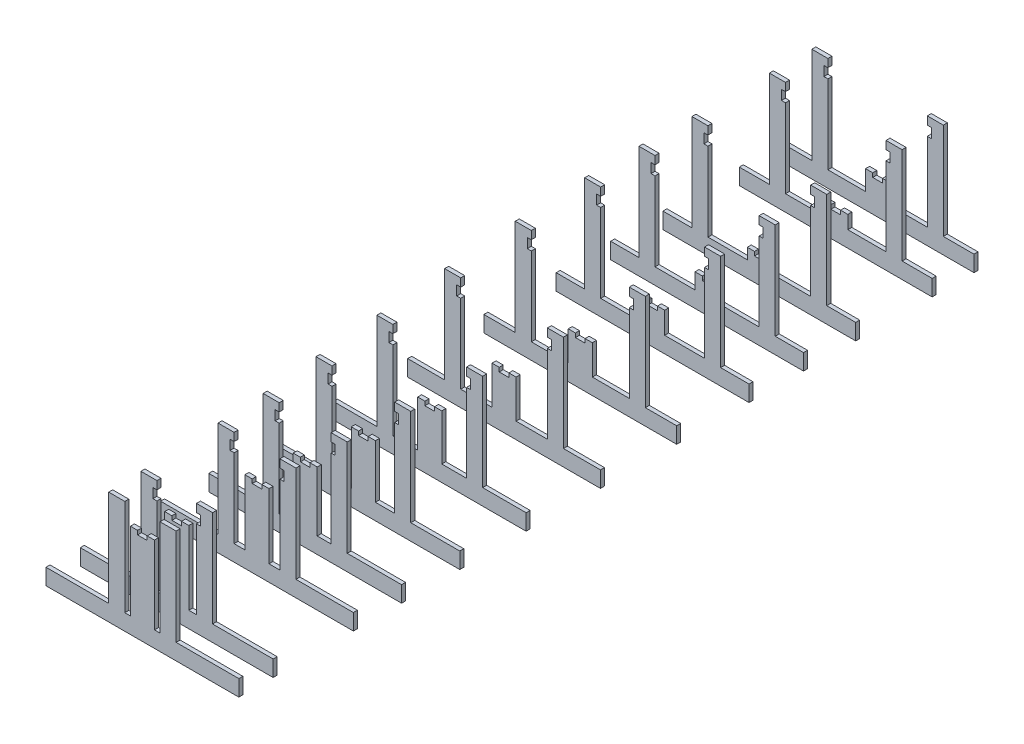
SolidWorks part; units mm, degrees
ref_plane "Front Plane" through (0, 0, 0) normal (0, 0, 1) x (1, 0, 0)
ref_plane "Top Plane" through (0, 0, 0) normal (0, 1, 0) x (1, 0, 0)
ref_plane "Right Plane" through (0, 0, 0) normal (1, 0, 0) x (0, 0, -1)
sketch "Sketch1" plane through (0, 0, 0) normal (0, 0, 1) x (1, 0, 0)
  line L0 (152.4, 0) -> (-152.4, 0)
  line L1 (-152.4, 0) -> (-152.4, 25.4)
  line L2 (-152.4, 25.4) -> (-103.9322, 25.4)
  line L3 (-103.9322, 25.4) -> (-103.9322, 177.8)
  line L4 (-103.9322, 177.8) -> (-78.5322, 177.8)
  line L5 (-78.5322, 177.8) -> (-78.5322, 165.1)
  line L6 (-78.5322, 25.4) -> (-19.05, 25.4)
  line L7 (-19.05, 25.4) -> (-19.05, 56.7311)
  line L9 (19.05, 56.7311) -> (19.05, 25.4)
  line L10 (19.05, 25.4) -> (78.5322, 25.4)
  line L12 (103.9322, 177.8) -> (78.5322, 177.8)
  line L15 (152.4, 25.4) -> (152.4, 0)
  line L16 (78.5322, 25.4) -> (78.5322, 149.86)
  line L17 (103.9322, 177.8) -> (103.9322, 25.4)
  line L18 (103.9322, 25.4) -> (152.4, 25.4)
  line L20 (7.62, 56.7311) -> (7.62, 50.3811)
  line L21 (7.62, 50.3811) -> (-7.62, 50.3811)
  line L22 (-7.62, 50.3811) -> (-7.62, 56.7311)
  line L23 (19.05, 56.7311) -> (7.62, 56.7311)
  line L24 (-7.62, 56.7311) -> (-19.05, 56.7311)
  line L25 (78.5322, 165.1) -> (78.5322, 177.8)
  line L26 (78.5322, 165.1) -> (84.8822, 165.1)
  line L28 (78.5322, 149.86) -> (84.8822, 149.86)
  line L29 (84.8822, 165.1) -> (84.8822, 149.86)
  line L30 (-78.5322, 149.86) -> (-78.5322, 25.4)
  line L31 (-78.5322, 165.1) -> (-84.8822, 165.1)
  line L33 (-78.5322, 149.86) -> (-84.8822, 149.86)
  line L34 (-84.8822, 165.1) -> (-84.8822, 149.86)
  point P0 (-91.2322, 177.8)
  point P3 (0, 0)
  point P4 (0, 0)
  point P20 (91.2322, 177.8)
  point P25 (0.3991, 53.8457)
  dimension "D2" = 182.4645
  dimension "D3" = 6.35
  dimension "D4" = 38.1
  dimension "D5" = 25.4
  dimension "D6" = 25.4
  dimension "D7" = 152.4
  dimension "D8" = 6.35
  dimension "D9" = 304.8
  dimension "D10" = 15.24
  dimension "D11" = 121.0689
  dimension "D12" = 15.24
  dimension "D13" = 12.7
  dimension "D14" = 6.35
  dimension "D15" = 15.24
  dimension "D16" = 12.7
  dimension "D17" = 7.62
sketch3d "3DSketch1"
  line L0 (152.5328, 0, 66.269) -> (-152.2672, 0, 66.269)
  line L1 (152.5328, 0, 66.269) -> (152.5328, 25.4, 66.269)
  line L2 (152.5328, 25.4, 66.269) -> (104.9842, 25.4, 66.269)
  line L3 (104.9842, 25.4, 66.269) -> (104.9842, 177.8, 66.269)
  line L4 (104.9842, 177.8, 66.269) -> (79.5842, 177.8, 66.269)
  line L6 (79.5842, 25.4, 66.269) -> (19.1828, 25.4, 66.269)
  line L7 (19.1828, 25.4, 66.269) -> (19.1828, 46.3854, 66.269)
  line L9 (-18.9172, 46.3854, 66.269) -> (-18.9172, 25.4, 66.269)
  line L10 (-18.9172, 25.4, 66.269) -> (-79.3186, 25.4, 66.269)
  line L12 (-79.3186, 177.8, 66.269) -> (-104.7186, 177.8, 66.269)
  line L13 (-104.7186, 177.8, 66.269) -> (-104.7186, 25.4, 66.269)
  line L14 (-104.7186, 25.4, 66.269) -> (-152.2672, 25.4, 66.269)
  line L15 (-152.2672, 25.4, 66.269) -> (-152.2672, 0, 66.269)
  line L17 (19.1828, 46.3854, 66.269) -> (7.7528, 46.3854, 66.269)
  line L19 (7.7528, 46.3854, 66.269) -> (7.7528, 40.0354, 66.269)
  line L20 (7.7528, 40.0354, 66.269) -> (-7.4872, 40.0354, 66.269)
  line L21 (-7.4872, 46.3854, 66.269) -> (-7.4872, 40.0354, 66.269)
  line L22 (-7.4872, 46.3854, 66.269) -> (-18.9172, 46.3854, 66.269)
  line L23 (79.5842, 177.8, 66.269) -> (79.5842, 165.1, 66.269)
  line L24 (79.5842, 165.1, 66.269) -> (85.9342, 165.1, 66.269)
  line L26 (79.5842, 149.86, 66.269) -> (85.9342, 149.86, 66.269)
  line L27 (85.9342, 165.1, 66.269) -> (85.9342, 149.86, 66.269)
  line L28 (-79.3186, 165.1, 66.269) -> (-85.6686, 165.1, 66.269)
  line L30 (-79.3186, 149.86, 66.269) -> (-85.6686, 149.86, 66.269)
  line L31 (-85.6686, 165.1, 66.269) -> (-85.6686, 149.86, 66.269)
  line L32 (79.5842, 149.86, 66.269) -> (79.5842, 25.4, 66.269)
  line L33 (-79.3186, 177.8, 66.269) -> (-79.3186, 165.1, 66.269)
  line L34 (-79.3186, 149.86, 66.269) -> (-79.3186, 25.4, 66.269)
  point P3 (0.1328, 0, 66.269)
  point P20 (-92.0186, 177.8, 66.269)
  point P21 (92.2842, 177.8, 66.269)
  dimension "D2" = 25.4
  dimension "D1" = 304.8
  dimension "D3" = 184.3028
  dimension "D4" = 25.4
  dimension "D5" = 38.1
  dimension "D6" = 152.4
  dimension "D7" = 131.4146
  dimension "D9" = 6.35
  dimension "D8" = 66.269
  dimension "D10" = 15.24
  dimension "D11" = 12.7
  dimension "D12" = 6.35
  dimension "D13" = 15.24
  dimension "D14" = 6.35
  dimension "D15" = 15.24
  dimension "D16" = 12.7
  dimension "D17" = 19.05
  dimension "D18" = 19.05
  dimension "D19" = 7.62
extrude "F0" add sketch "Sketch1" along normal blind 6.35
extrude "F1" add sketch "3DSketch1" along direction (0, 0, -1) on the side of the normal blind 6.35 separate body contours L0 L15 L14 L13 L12 L33 L28 L31 L30 L34 L10 L9 L22 L21 L20 L19 L17 L7 L6 L32 L26 L27 L24 L23 L4 L3 L2 L1
sketch3d "3DSketch2"
  line L0 (-152.4, 0, 186.919) -> (152.4, 0, 186.919)
  line L1 (152.4, 0, 186.919) -> (152.4, 25.4, 186.919)
  line L2 (152.4, 25.4, 186.919) -> (106.5766, 25.4, 186.919)
  line L3 (106.5766, 25.4, 186.919) -> (106.5766, 177.8, 186.919)
  line L4 (106.5766, 177.8, 186.919) -> (81.1766, 177.8, 186.919)
  line L6 (81.1766, 25.4, 186.919) -> (19.05, 25.4, 186.919)
  line L7 (19.05, 25.4, 186.919) -> (19.05, 42.5995, 186.919)
  line L9 (-19.05, 42.5995, 186.919) -> (-19.05, 25.4, 186.919)
  line L10 (-19.05, 25.4, 186.919) -> (-81.1766, 25.4, 186.919)
  line L12 (-81.1766, 177.8, 186.919) -> (-106.5766, 177.8, 186.919)
  line L13 (-106.5766, 177.8, 186.919) -> (-106.5766, 25.4, 186.919)
  line L14 (-106.5766, 25.4, 186.919) -> (-152.4, 25.4, 186.919)
  line L15 (-152.4, 25.4, 186.919) -> (-152.4, 0, 186.919)
  line L16 (-19.05, 42.5995, 186.919) -> (-7.62, 42.5995, 186.919)
  line L17 (-152.2672, 0, 72.619) -> (152.5328, 0, 72.619) construction
  line L19 (-7.62, 42.5995, 186.919) -> (-7.62, 36.2495, 186.919)
  line L20 (-7.62, 36.2495, 186.919) -> (7.62, 36.2495, 186.919)
  line L21 (7.62, 42.5995, 186.919) -> (7.62, 36.2495, 186.919)
  line L22 (7.62, 42.5995, 186.919) -> (19.05, 42.5995, 186.919)
  line L23 (-81.1766, 177.8, 186.919) -> (-81.1766, 165.1, 186.919)
  line L24 (-81.1766, 165.1, 186.919) -> (-87.5266, 165.1, 186.919)
  line L26 (-81.1766, 149.86, 186.919) -> (-87.5266, 149.86, 186.919)
  line L27 (-87.5266, 165.1, 186.919) -> (-87.5266, 149.86, 186.919)
  line L28 (81.1766, 165.1, 186.919) -> (87.5266, 165.1, 186.919)
  line L30 (81.1766, 149.86, 186.919) -> (87.5266, 149.86, 186.919)
  line L31 (87.5266, 165.1, 186.919) -> (87.5266, 149.86, 186.919)
  line L32 (-81.1766, 149.86, 186.919) -> (-81.1766, 25.4, 186.919)
  line L33 (81.1766, 177.8, 186.919) -> (81.1766, 165.1, 186.919)
  line L34 (81.1766, 149.86, 186.919) -> (81.1766, 25.4, 186.919)
  point P3 (0, 0, 186.919)
  point P18 (-93.8766, 177.8, 186.919)
  point P22 (93.8766, 177.8, 186.919)
  dimension "D2" = 152.4
  dimension "D1" = 25.4
  dimension "D3" = 25.4
  dimension "D4" = 38.1
  dimension "D5" = 187.7532
  dimension "D6" = 135.2005
  dimension "D9" = 15.24
  dimension "D7" = 114.3
  dimension "D8" = 304.8
  dimension "D10" = 6.35
  dimension "D11" = 12.7
  dimension "D12" = 15.24
  dimension "D13" = 6.35
  dimension "D14" = 12.7
  dimension "D15" = 7.62
  dimension "D16" = 6.35
extrude "F2" add sketch "3DSketch2" along direction (0, 0, -1) on the side against the normal blind 6.35 separate body contours L13 L14 L15 L0 L1 L2 L3 L4 L33 L28 L31 L30 L34 L6 L7 L22 L21 L20 L19 L16 L9 L10 L32 L26 L27 L24 L23 L12
sketch3d "3DSketch3"
  line L1 (-19.05, 50.2445, 269.469) -> (-7.62, 50.2445, 269.469)
  line L2 (-152.4, 0, 269.469) -> (152.4, 0, 269.469)
  line L3 (152.4, 0, 269.469) -> (152.4, 25.4, 269.469)
  line L4 (152.4, 25.4, 269.469) -> (107.6828, 25.4, 269.469)
  line L5 (107.6828, 25.4, 269.469) -> (107.6828, 177.8, 269.469)
  line L6 (107.6828, 177.8, 269.469) -> (82.2828, 177.8, 269.469)
  line L8 (82.2828, 25.4, 269.469) -> (19.05, 25.4, 269.469)
  line L9 (19.05, 25.4, 269.469) -> (19.05, 50.2445, 269.469)
  line L11 (-19.05, 50.2445, 269.469) -> (-19.05, 25.4, 269.469)
  line L12 (-19.05, 25.4, 269.469) -> (-82.2828, 25.4, 269.469)
  line L14 (-82.2828, 177.8, 269.469) -> (-107.6828, 177.8, 269.469)
  line L15 (-107.6828, 177.8, 269.469) -> (-107.6828, 25.4, 269.469)
  line L16 (-107.6828, 25.4, 269.469) -> (-152.4, 25.4, 269.469)
  line L17 (-152.4, 25.4, 269.469) -> (-152.4, 0, 269.469)
  line L19 (-7.62, 50.2445, 269.469) -> (-7.62, 43.8945, 269.469)
  line L20 (-7.62, 43.8945, 269.469) -> (7.62, 43.8945, 269.469)
  line L21 (7.62, 50.2445, 269.469) -> (7.62, 43.8945, 269.469)
  line L22 (7.62, 50.2445, 269.469) -> (19.05, 50.2445, 269.469)
  line L23 (-82.2828, 177.8, 269.469) -> (-82.2828, 165.1, 269.469)
  line L24 (-82.2828, 165.1, 269.469) -> (-88.6328, 165.1, 269.469)
  line L26 (-82.2828, 149.86, 269.469) -> (-88.6328, 149.86, 269.469)
  line L27 (-88.6328, 165.1, 269.469) -> (-88.6328, 149.86, 269.469)
  line L28 (82.2828, 165.1, 269.469) -> (88.6328, 165.1, 269.469)
  line L30 (82.2828, 149.86, 269.469) -> (88.6328, 149.86, 269.469)
  line L31 (88.6328, 165.1, 269.469) -> (88.6328, 149.86, 269.469)
  line L32 (-82.2828, 149.86, 269.469) -> (-82.2828, 25.4, 269.469)
  line L33 (82.2828, 177.8, 269.469) -> (82.2828, 165.1, 269.469)
  line L34 (82.2828, 149.86, 269.469) -> (82.2828, 25.4, 269.469)
  line L36 (-152.4, 0, 193.269) -> (152.4, 0, 193.269) construction
  point P2 (-94.9828, 177.8, 269.469)
  point P3 (94.9828, 177.8, 269.469)
  point P6 (0, 0, 269.469)
  dimension "D16" = 76.2
  dimension "D2" = 304.8
  dimension "D3" = 25.4
  dimension "D4" = 152.4
  dimension "D5" = 25.4
  dimension "D6" = 189.9655
  dimension "D7" = 38.1
  dimension "D8" = 127.5555
  dimension "D9" = 6.35
  dimension "D10" = 15.24
  dimension "D11" = 12.7
  dimension "D12" = 6.35
  dimension "D13" = 15.24
  dimension "D14" = 19.05
  dimension "D15" = 19.05
  dimension "D17" = 7.62
extrude "F3" add sketch "3DSketch3" along normal blind 6.35 separate body contours L12 L32 L26 L27 L24 L23 L14 L15 L16 L17 L2 L3 L4 L5 L6 L33 L28 L31 L30 L34 L8 L9 L22 L21 L20 L19 L1 L11
sketch3d "3DSketch4"
  line L1 (-19.05, 59.7774, 355.6) -> (-7.62, 59.7774, 355.6)
  line L2 (152.4, 0, 355.6) -> (-152.4, 0, 355.6)
  line L3 (-152.4, 0, 355.6) -> (-152.4, 25.4, 355.6)
  line L4 (-152.4, 25.4, 355.6) -> (-107.4723, 25.4, 355.6)
  line L5 (-107.4723, 25.4, 355.6) -> (-107.4723, 177.8, 355.6)
  line L6 (-107.4723, 177.8, 355.6) -> (-82.0723, 177.8, 355.6)
  line L8 (-82.0723, 25.4, 355.6) -> (-19.05, 25.4, 355.6)
  line L9 (-19.05, 25.4, 355.6) -> (-19.05, 59.7774, 355.6)
  line L11 (19.05, 59.7774, 355.6) -> (19.05, 25.4, 355.6)
  line L12 (19.05, 25.4, 355.6) -> (82.0723, 25.4, 355.6)
  line L14 (82.0723, 177.8, 355.6) -> (107.4723, 177.8, 355.6)
  line L15 (107.4723, 177.8, 355.6) -> (107.4723, 25.4, 355.6)
  line L16 (107.4723, 25.4, 355.6) -> (152.4, 25.4, 355.6)
  line L17 (152.4, 25.4, 355.6) -> (152.4, 0, 355.6)
  line L19 (-7.62, 59.7774, 355.6) -> (-7.62, 53.4274, 355.6)
  line L20 (-7.62, 53.4274, 355.6) -> (7.62, 53.4274, 355.6)
  line L21 (7.62, 59.7774, 355.6) -> (7.62, 53.4274, 355.6)
  line L22 (7.62, 59.7774, 355.6) -> (19.05, 59.7774, 355.6)
  line L23 (-82.0723, 177.8, 355.6) -> (-82.0723, 165.1, 355.6)
  line L24 (-82.0723, 165.1, 355.6) -> (-88.4223, 165.1, 355.6)
  line L26 (-82.0723, 149.86, 355.6) -> (-88.4223, 149.86, 355.6)
  line L27 (-88.4223, 165.1, 355.6) -> (-88.4223, 149.86, 355.6)
  line L28 (82.0723, 165.1, 355.6) -> (88.4223, 165.1, 355.6)
  line L30 (82.0723, 149.86, 355.6) -> (88.4223, 149.86, 355.6)
  line L31 (88.4223, 165.1, 355.6) -> (88.4223, 149.86, 355.6)
  line L32 (-82.0723, 149.86, 355.6) -> (-82.0723, 25.4, 355.6)
  line L33 (82.0723, 177.8, 355.6) -> (82.0723, 165.1, 355.6)
  line L34 (82.0723, 149.86, 355.6) -> (82.0723, 25.4, 355.6)
  point P6 (0, 0, 355.6)
  point P21 (-94.7723, 177.8, 355.6)
  point P22 (94.7723, 177.8, 355.6)
  dimension "D1" = 304.8
  dimension "D2" = 25.4
  dimension "D3" = 152.4
  dimension "D4" = 25.4
  dimension "D5" = 38.1
  dimension "D6" = 189.5445
  dimension "D7" = 118.0226
  dimension "D9" = 6.35
  dimension "D8" = 79.781
  dimension "D16" = 7.62
  dimension "D10" = 15.24
  dimension "D11" = 12.7
  dimension "D12" = 6.35
  dimension "D13" = 15.24
  dimension "D14" = 19.05
  dimension "D15" = 19.05
extrude "F4" add sketch "3DSketch4" along direction (0, 0, 1) on the side of the normal blind 6.35 separate body contours L4 L5 L6 L23 L24 L27 L26 L32 L8 L9 L1 L19 L20 L21 L22 L11 L12 L34 L30 L31 L28 L33 L14 L15 L16 L17 L2 L3
sketch3d "3DSketch5"
  line L1 (19.05, 72.4289, 469.9) -> (7.62, 72.4289, 469.9)
  line L2 (152.4, 0, 469.9) -> (-152.4, 0, 469.9)
  line L3 (-152.4, 0, 469.9) -> (-152.4, 25.4, 469.9)
  line L4 (-152.4, 25.4, 469.9) -> (-102.8282, 25.4, 469.9)
  line L5 (-102.8282, 25.4, 469.9) -> (-102.8282, 177.8, 469.9)
  line L6 (-102.8282, 177.8, 469.9) -> (-77.4282, 177.8, 469.9)
  line L8 (-77.4282, 25.4, 469.9) -> (-19.05, 25.4, 469.9)
  line L9 (-19.05, 25.4, 469.9) -> (-19.05, 72.4289, 469.9)
  line L11 (19.05, 72.4289, 469.9) -> (19.05, 25.4, 469.9)
  line L12 (19.05, 25.4, 469.9) -> (77.4282, 25.4, 469.9)
  line L14 (77.4282, 177.8, 469.9) -> (102.8282, 177.8, 469.9)
  line L15 (102.8282, 177.8, 469.9) -> (102.8282, 25.4, 469.9)
  line L16 (102.8282, 25.4, 469.9) -> (152.4, 25.4, 469.9)
  line L17 (152.4, 25.4, 469.9) -> (152.4, 0, 469.9)
  line L19 (7.62, 72.4289, 469.9) -> (7.62, 66.0789, 469.9)
  line L20 (7.62, 66.0789, 469.9) -> (-7.62, 66.0789, 469.9)
  line L21 (-7.62, 72.4289, 469.9) -> (-7.62, 66.0789, 469.9)
  line L22 (77.4282, 165.1, 469.9) -> (83.7782, 165.1, 469.9)
  line L24 (77.4282, 149.7642, 469.9) -> (83.7782, 149.7642, 469.9)
  line L25 (83.7782, 165.1, 469.9) -> (83.7782, 149.7642, 469.9)
  line L26 (-77.4282, 165.1, 469.9) -> (-83.7782, 165.1, 469.9)
  line L28 (-77.4282, 149.7642, 469.9) -> (-83.7782, 149.7642, 469.9)
  line L29 (-83.7782, 165.1, 469.9) -> (-83.7782, 149.7642, 469.9)
  line L30 (-7.62, 72.4289, 469.9) -> (-19.05, 72.4289, 469.9)
  line L31 (77.4282, 177.8, 469.9) -> (77.4282, 165.1, 469.9)
  line L32 (77.4282, 149.7642, 469.9) -> (77.4282, 25.4, 469.9)
  line L33 (-77.4282, 177.8, 469.9) -> (-77.4282, 165.1, 469.9)
  line L34 (-77.4282, 149.7642, 469.9) -> (-77.4282, 25.4, 469.9)
  point P6 (0, 0, 469.9)
  point P21 (-90.1282, 177.8, 469.9)
  point P22 (90.1282, 177.8, 469.9)
  dimension "D1" = 304.8
  dimension "D2" = 25.4
  dimension "D3" = 152.4
  dimension "D4" = 180.2564
  dimension "D5" = 25.4
  dimension "D6" = 38.1
  dimension "D7" = 105.3711
  dimension "D9" = 15.24
  dimension "D8" = 107.95
  dimension "D14" = 7.62
  dimension "D10" = 6.35
  dimension "D11" = 12.7
  dimension "D12" = 6.35
  dimension "D13" = 15.3358
extrude "F5" add sketch "3DSketch5" along direction (0, 0, 1) on the side against the normal blind 6.35 separate body contours L2 L3 L4 L5 L6 L33 L26 L29 L28 L34 L8 L9 L30 L21 L20 L19 L1 L11 L12 L32 L24 L25 L22 L31 L14 L15 L16 L17
sketch3d "3DSketch6"
  line L0 (68.6198, 177.8, 590.55) -> (68.6198, 165.1, 590.55)
  line L2 (-152.2755, 0, 590.55) -> (152.5245, 0, 590.55)
  line L3 (152.5245, 0, 590.55) -> (152.5245, 25.4, 590.55)
  line L4 (152.5245, 25.4, 590.55) -> (94.0198, 25.4, 590.55)
  line L5 (94.0198, 25.4, 590.55) -> (94.0198, 177.8, 590.55)
  line L6 (94.0198, 177.8, 590.55) -> (68.6198, 177.8, 590.55)
  line L8 (68.6198, 25.4, 590.55) -> (19.1745, 25.4, 590.55)
  line L9 (19.1745, 25.4, 590.55) -> (19.1745, 85.804, 590.55)
  line L11 (-18.9255, 85.804, 590.55) -> (-18.9255, 25.4, 590.55)
  line L12 (-18.9255, 25.4, 590.55) -> (-68.3707, 25.4, 590.55)
  line L14 (-68.3707, 177.8, 590.55) -> (-93.7707, 177.8, 590.55)
  line L15 (-93.7707, 177.8, 590.55) -> (-93.7707, 25.4, 590.55)
  line L16 (-93.7707, 25.4, 590.55) -> (-152.2755, 25.4, 590.55)
  line L17 (-152.2755, 25.4, 590.55) -> (-152.2755, 0, 590.55)
  line L18 (7.7445, 85.804, 590.55) -> (7.7445, 79.454, 590.55)
  line L19 (7.7445, 79.454, 590.55) -> (-7.4955, 79.454, 590.55)
  line L20 (-7.4955, 85.804, 590.55) -> (-7.4955, 79.454, 590.55)
  line L21 (68.6198, 165.1, 590.55) -> (74.9698, 165.1, 590.55)
  line L23 (68.6198, 149.86, 590.55) -> (74.9698, 149.86, 590.55)
  line L24 (74.9698, 165.1, 590.55) -> (74.9698, 149.86, 590.55)
  line L25 (-68.3707, 165.1, 590.55) -> (-74.7207, 165.1, 590.55)
  line L27 (-68.3707, 149.86, 590.55) -> (-74.7207, 149.86, 590.55)
  line L28 (-74.7207, 165.1, 590.55) -> (-74.7207, 149.86, 590.55)
  line L29 (68.6198, 149.86, 590.55) -> (68.6198, 25.4, 590.55)
  line L30 (-68.3707, 177.8, 590.55) -> (-68.3707, 165.1, 590.55)
  line L31 (-68.3707, 149.86, 590.55) -> (-68.3707, 25.4, 590.55)
  line L32 (19.1745, 85.804, 590.55) -> (7.7445, 85.804, 590.55)
  line L33 (-7.4955, 85.804, 590.55) -> (-18.9255, 85.804, 590.55)
  point P6 (0.1245, 0, 590.55)
  point P21 (-81.0707, 177.8, 590.55)
  point P22 (81.3198, 177.8, 590.55)
  point P31 (0.1245, 79.454, 590.55)
  dimension "D1" = 25.4
  dimension "D2" = 152.4
  dimension "D3" = 25.4
  dimension "D4" = 38.1
  dimension "D5" = 304.8
  dimension "D6" = 162.3905
  dimension "D7" = 91.996
  dimension "D9" = 12.7
  dimension "D8" = 114.3
  dimension "D10" = 15.24
  dimension "D11" = 6.35
  dimension "D12" = 15.24
  dimension "D13" = 6.35
  dimension "D14" = 7.62
extrude "F6" add sketch "3DSketch6" along direction (0, 0, 1) on the side of the normal blind 6.35 separate body contours L15 L16 L17 L2 L3 L4 L5 L6 L0 L21 L24 L23 L29 L8 L9 L32 L18 L19 L20 L33 L11 L12 L31 L27 L28 L25 L30 L14
sketch3d "3DSketch7"
  line L0 (58.204, 177.8, 707.9085) -> (58.204, 165.1, 707.9085)
  line L2 (152.4, 0, 707.9085) -> (-152.4, 0, 707.9085)
  line L3 (-152.4, 0, 707.9085) -> (-152.4, 25.4, 707.9085)
  line L4 (-152.4, 25.4, 707.9085) -> (-83.604, 25.4, 707.9085)
  line L5 (-83.604, 25.4, 707.9085) -> (-83.604, 177.8, 707.9085)
  line L6 (-83.604, 177.8, 707.9085) -> (-58.204, 177.8, 707.9085)
  line L8 (-58.204, 25.4, 707.9085) -> (-19.05, 25.4, 707.9085)
  line L9 (-19.05, 25.4, 707.9085) -> (-19.05, 98.1126, 707.9085)
  line L11 (19.05, 98.1126, 707.9085) -> (19.05, 25.4, 707.9085)
  line L12 (19.05, 25.4, 707.9085) -> (58.204, 25.4, 707.9085)
  line L14 (58.204, 177.8, 707.9085) -> (83.604, 177.8, 707.9085)
  line L15 (83.604, 177.8, 707.9085) -> (83.604, 25.4, 707.9085)
  line L16 (83.604, 25.4, 707.9085) -> (152.4, 25.4, 707.9085)
  line L17 (152.4, 25.4, 707.9085) -> (152.4, 0, 707.9085)
  line L18 (7.62, 98.1126, 707.9085) -> (7.62, 91.7626, 707.9085)
  line L19 (7.62, 91.7626, 707.9085) -> (-7.62, 91.7626, 707.9085)
  line L20 (-7.62, 98.1126, 707.9085) -> (-7.62, 91.7626, 707.9085)
  line L21 (-58.204, 165.1, 707.9085) -> (-64.554, 165.1, 707.9085)
  line L23 (-58.204, 149.86, 707.9085) -> (-64.554, 149.86, 707.9085)
  line L24 (-64.554, 165.1, 707.9085) -> (-64.554, 149.86, 707.9085)
  line L25 (58.204, 165.1, 707.9085) -> (64.554, 165.1, 707.9085)
  line L27 (58.204, 149.86, 707.9085) -> (64.554, 149.86, 707.9085)
  line L28 (64.554, 165.1, 707.9085) -> (64.554, 149.86, 707.9085)
  line L29 (58.204, 149.86, 707.9085) -> (58.204, 25.4, 707.9085)
  line L30 (-58.204, 177.8, 707.9085) -> (-58.204, 165.1, 707.9085)
  line L31 (-58.204, 149.86, 707.9085) -> (-58.204, 25.4, 707.9085)
  line L32 (-19.05, 98.1126, 707.9085) -> (-7.62, 98.1126, 707.9085)
  line L33 (7.62, 98.1126, 707.9085) -> (19.05, 98.1126, 707.9085)
  point P6 (0, 0, 707.9085)
  point P21 (-70.904, 177.8, 707.9085)
  point P22 (70.904, 177.8, 707.9085)
  dimension "D1" = 304.8
  dimension "D2" = 25.4
  dimension "D3" = 152.4
  dimension "D4" = 25.4
  dimension "D5" = 38.1
  dimension "D6" = 141.8079
  dimension "D7" = 79.6874
  dimension "D8" = 12.7
  dimension "D9" = 15.24
  dimension "D10" = 6.35
  dimension "D11" = 15.24
  dimension "D12" = 6.35
  dimension "D13" = 7.62
extrude "F7" add sketch "3DSketch7" along direction (0, 0, 1) on the side of the normal blind 6.35 separate body contours L4 L5 L6 L30 L21 L24 L23 L31 L8 L9 L32 L20 L19 L18 L33 L11 L12 L29 L27 L28 L25 L0 L14 L15 L16 L17 L2 L3
sketch3d "3DSketch8"
  line L0 (-19.05, 109.752, 812.8) -> (-7.62, 109.752, 812.8)
  line L2 (-152.4, 0, 812.8) -> (152.4, 0, 812.8)
  line L3 (152.4, 0, 812.8) -> (152.4, 25.4, 812.8)
  line L4 (152.4, 25.4, 812.8) -> (74.9005, 25.4, 812.8)
  line L5 (74.9005, 25.4, 812.8) -> (74.9005, 177.8, 812.8)
  line L6 (74.9005, 177.8, 812.8) -> (49.5005, 177.8, 812.8)
  line L8 (49.5005, 25.4, 812.8) -> (19.05, 25.4, 812.8)
  line L9 (19.05, 25.4, 812.8) -> (19.05, 109.752, 812.8)
  line L11 (-19.05, 109.752, 812.8) -> (-19.05, 25.4, 812.8)
  line L12 (-19.05, 25.4, 812.8) -> (-49.5005, 25.4, 812.8)
  line L14 (-49.5005, 177.8, 812.8) -> (-74.9005, 177.8, 812.8)
  line L15 (-74.9005, 177.8, 812.8) -> (-74.9005, 25.4, 812.8)
  line L16 (-74.9005, 25.4, 812.8) -> (-152.4, 25.4, 812.8)
  line L17 (-152.4, 25.4, 812.8) -> (-152.4, 0, 812.8)
  line L18 (-7.62, 109.752, 812.8) -> (-7.62, 103.402, 812.8)
  line L19 (-7.62, 103.402, 812.8) -> (7.62, 103.402, 812.8)
  line L20 (7.62, 109.752, 812.8) -> (7.62, 103.402, 812.8)
  line L21 (-49.5005, 165.1, 812.8) -> (-55.8505, 165.1, 812.8)
  line L23 (-49.5005, 149.86, 812.8) -> (-55.8505, 149.86, 812.8)
  line L24 (-55.8505, 165.1, 812.8) -> (-55.8505, 149.86, 812.8)
  line L25 (49.5005, 165.1, 812.8) -> (55.8505, 165.1, 812.8)
  line L27 (49.5005, 149.86, 812.8) -> (55.8505, 149.86, 812.8)
  line L28 (55.8505, 165.1, 812.8) -> (55.8505, 149.86, 812.8)
  line L29 (7.62, 109.752, 812.8) -> (19.05, 109.752, 812.8)
  line L30 (-49.5005, 177.8, 812.8) -> (-49.5005, 165.1, 812.8)
  line L31 (-49.5005, 149.86, 812.8) -> (-49.5005, 25.4, 812.8)
  line L32 (49.5005, 25.4, 812.8) -> (49.5005, 149.86, 812.8)
  line L33 (49.5005, 165.1, 812.8) -> (49.5005, 177.8, 812.8)
  point P6 (0, 0, 812.8)
  point P21 (-62.2005, 177.8, 812.8)
  point P22 (62.2005, 177.8, 812.8)
  dimension "D1" = 304.8
  dimension "D2" = 25.4
  dimension "D3" = 152.4
  dimension "D4" = 25.4
  dimension "D5" = 38.1
  dimension "D6" = 124.4009
  dimension "D7" = 68.048
  dimension "D8" = 7.62
  dimension "D9" = 12.7
  dimension "D10" = 15.24
  dimension "D11" = 6.35
  dimension "D12" = 15.24
  dimension "D13" = 6.35
  dimension "D14" = 98.5415
extrude "F8" add sketch "3DSketch8" along direction (0, 0, -1) on the side against the normal blind 6.35 separate body contours L15 L16 L17 L2 L3 L4 L5 L6 L33 L25 L28 L27 L32 L8 L9 L29 L20 L19 L18 L0 L11 L12 L31 L23 L24 L21 L30 L14
sketch3d "3DSketch9"
  line L0 (-40.9127, 177.8, 904.875) -> (-40.9127, 165.1, 904.875)
  line L1 (-40.9127, 165.1, 904.875) -> (-47.2627, 165.1, 904.875)
  line L2 (152.5212, 0, 904.875) -> (-152.2788, 0, 904.875)
  line L3 (-152.2788, 0, 904.875) -> (-152.2788, 25.4, 904.875)
  line L4 (-152.2788, 25.4, 904.875) -> (-66.3127, 25.4, 904.875)
  line L5 (-66.3127, 25.4, 904.875) -> (-66.3127, 177.8, 904.875)
  line L6 (-66.3127, 177.8, 904.875) -> (-40.9127, 177.8, 904.875)
  line L8 (-40.9127, 25.4, 904.875) -> (-18.9288, 25.4, 904.875)
  line L9 (-18.9288, 25.4, 904.875) -> (-18.9288, 119.8783, 904.875)
  line L11 (19.1712, 119.8783, 904.875) -> (19.1712, 25.4, 904.875)
  line L12 (19.1712, 25.4, 904.875) -> (41.1552, 25.4, 904.875)
  line L14 (41.1552, 177.8, 904.875) -> (66.5552, 177.8, 904.875)
  line L15 (66.5552, 177.8, 904.875) -> (66.5552, 25.4, 904.875)
  line L16 (66.5552, 25.4, 904.875) -> (152.5212, 25.4, 904.875)
  line L17 (152.5212, 25.4, 904.875) -> (152.5212, 0, 904.875)
  line L19 (-40.9127, 149.86, 904.875) -> (-47.2627, 149.86, 904.875)
  line L20 (-47.2627, 165.1, 904.875) -> (-47.2627, 149.86, 904.875)
  line L21 (41.1552, 165.1, 904.875) -> (47.5052, 165.1, 904.875)
  line L23 (41.1552, 149.86, 904.875) -> (47.5052, 149.86, 904.875)
  line L24 (47.5052, 165.1, 904.875) -> (47.5052, 149.86, 904.875)
  line L26 (-7.4988, 119.8783, 904.875) -> (-7.4988, 113.5283, 904.875)
  line L27 (-7.4988, 113.5283, 904.875) -> (7.7412, 113.5283, 904.875)
  line L28 (7.7412, 119.8783, 904.875) -> (7.7412, 113.5283, 904.875)
  line L29 (-40.9127, 149.86, 904.875) -> (-40.9127, 25.4, 904.875)
  line L30 (41.1552, 177.8, 904.875) -> (41.1552, 165.1, 904.875)
  line L31 (41.1552, 149.86, 904.875) -> (41.1552, 25.4, 904.875)
  line L32 (-18.9288, 119.8783, 904.875) -> (-7.4988, 119.8783, 904.875)
  line L33 (7.7412, 119.8783, 904.875) -> (19.1712, 119.8783, 904.875)
  point P0 (-53.6127, 177.8, 904.875)
  point P1 (53.8552, 177.8, 904.875)
  point P6 (0.1212, 0, 904.875)
  dimension "D1" = 304.8
  dimension "D2" = 25.4
  dimension "D3" = 152.4
  dimension "D4" = 25.4
  dimension "D5" = 38.1
  dimension "D6" = 107.4679
  dimension "D7" = 85.725
  dimension "D9" = 15.24
  dimension "D8" = 57.9217
  dimension "D10" = 6.35
  dimension "D11" = 15.24
  dimension "D12" = 6.35
  dimension "D13" = 12.7
  dimension "D14" = 7.62
extrude "F9" add sketch "3DSketch9" along direction (0, 0, -1) on the side against the normal blind 6.35 separate body contours L4 L5 L6 L0 L1 L20 L19 L29 L8 L9 L32 L26 L27 L28 L33 L11 L12 L31 L23 L24 L21 L30 L14 L15 L16 L17 L2 L3
sketch3d "3DSketch10"
  line L0 (-36.0765, 177.8, 981.075) -> (-36.0765, 165.1, 981.075)
  line L1 (-36.0765, 165.1, 981.075) -> (-42.4265, 165.1, 981.075)
  line L2 (-152.2788, 0, 981.075) -> (152.5212, 0, 981.075)
  line L3 (152.5212, 0, 981.075) -> (152.5212, 25.4, 981.075)
  line L4 (152.5212, 25.4, 981.075) -> (61.719, 25.4, 981.075)
  line L5 (61.719, 25.4, 981.075) -> (61.719, 177.8, 981.075)
  line L6 (61.719, 177.8, 981.075) -> (36.319, 177.8, 981.075)
  line L8 (36.319, 25.4, 981.075) -> (19.1712, 25.4, 981.075)
  line L9 (19.1712, 25.4, 981.075) -> (19.1712, 128.3127, 981.075)
  line L11 (-18.9288, 128.3127, 981.075) -> (-18.9288, 25.4, 981.075)
  line L12 (-18.9288, 25.4, 981.075) -> (-36.0765, 25.4, 981.075)
  line L14 (-36.0765, 177.8, 981.075) -> (-61.4765, 177.8, 981.075)
  line L15 (-61.4765, 177.8, 981.075) -> (-61.4765, 25.4, 981.075)
  line L16 (-61.4765, 25.4, 981.075) -> (-152.2788, 25.4, 981.075)
  line L17 (-152.2788, 25.4, 981.075) -> (-152.2788, 0, 981.075)
  line L19 (-36.0765, 149.86, 981.075) -> (-42.4265, 149.86, 981.075)
  line L20 (-42.4265, 165.1, 981.075) -> (-42.4265, 149.86, 981.075)
  line L21 (36.319, 165.1, 981.075) -> (42.669, 165.1, 981.075)
  line L23 (36.319, 149.86, 981.075) -> (42.669, 149.86, 981.075)
  line L24 (42.669, 165.1, 981.075) -> (42.669, 149.86, 981.075)
  line L26 (-7.4988, 128.3127, 981.075) -> (-7.4988, 121.9627, 981.075)
  line L27 (-7.4988, 121.9627, 981.075) -> (7.7412, 121.9627, 981.075)
  line L28 (7.7412, 128.3127, 981.075) -> (7.7412, 121.9627, 981.075)
  line L29 (-36.0765, 149.86, 981.075) -> (-36.0765, 25.4, 981.075)
  line L30 (36.319, 25.4, 981.075) -> (36.319, 149.86, 981.075)
  line L31 (36.319, 165.1, 981.075) -> (36.319, 177.8, 981.075)
  line L32 (-18.9288, 128.3127, 981.075) -> (-7.4988, 128.3127, 981.075)
  line L33 (7.7412, 128.3127, 981.075) -> (19.1712, 128.3127, 981.075)
  point P6 (0.1212, 0, 981.075)
  point P21 (-48.7765, 177.8, 981.075)
  point P22 (49.019, 177.8, 981.075)
  dimension "D1" = 304.8
  dimension "D2" = 38.1
  dimension "D3" = 25.4
  dimension "D4" = 152.4
  dimension "D5" = 25.4
  dimension "D6" = 97.7955
  dimension "D7" = 49.4873
  dimension "D9" = 12.7
  dimension "D8" = 69.85
  dimension "D10" = 6.35
  dimension "D11" = 15.24
  dimension "D12" = 15.24
  dimension "D13" = 6.35
  dimension "D14" = 7.62
extrude "F10" add sketch "3DSketch10" along direction (0, 0, -1) on the side against the normal blind 6.35 separate body contours L2 L3 L4 L5 L6 L31 L21 L24 L23 L30 L8 L9 L33 L28 L27 L26 L32 L11 L12 L29 L19 L20 L1 L0 L14 L15 L16 L17
sketch3d "3DSketch11"
  line L0 (-30.9715, 177.8, 1108.075) -> (-30.9715, 165.1, 1108.075)
  line L1 (-30.9715, 165.1, 1108.075) -> (-37.3215, 165.1, 1108.075)
  line L2 (-152.122, 0, 1108.075) -> (152.678, 0, 1108.075)
  line L3 (152.678, 0, 1108.075) -> (152.678, 25.4, 1108.075)
  line L4 (152.678, 25.4, 1108.075) -> (56.9275, 25.4, 1108.075)
  line L5 (56.9275, 25.4, 1108.075) -> (56.9275, 177.8, 1108.075)
  line L6 (56.9275, 177.8, 1108.075) -> (31.5275, 177.8, 1108.075)
  line L8 (31.5275, 25.4, 1108.075) -> (19.328, 25.4, 1108.075)
  line L9 (19.328, 25.4, 1108.075) -> (19.328, 141.4782, 1108.075)
  line L11 (-18.772, 141.4782, 1108.075) -> (-18.772, 25.4, 1108.075)
  line L12 (-18.772, 25.4, 1108.075) -> (-30.9715, 25.4, 1108.075)
  line L14 (-30.9715, 177.8, 1108.075) -> (-56.3715, 177.8, 1108.075)
  line L15 (-56.3715, 177.8, 1108.075) -> (-56.3715, 25.4, 1108.075)
  line L16 (-56.3715, 25.4, 1108.075) -> (-152.122, 25.4, 1108.075)
  line L17 (-152.122, 25.4, 1108.075) -> (-152.122, 0, 1108.075)
  line L19 (-30.9715, 149.86, 1108.075) -> (-37.3215, 149.86, 1108.075)
  line L20 (-37.3215, 165.1, 1108.075) -> (-37.3215, 149.86, 1108.075)
  line L21 (31.5275, 165.1, 1108.075) -> (37.8775, 165.1, 1108.075)
  line L23 (31.5275, 149.86, 1108.075) -> (37.8775, 149.86, 1108.075)
  line L24 (37.8775, 165.1, 1108.075) -> (37.8775, 149.86, 1108.075)
  line L26 (-7.342, 141.4782, 1108.075) -> (-7.342, 135.1282, 1108.075)
  line L27 (-7.342, 135.1282, 1108.075) -> (7.898, 135.1282, 1108.075)
  line L28 (7.898, 141.4782, 1108.075) -> (7.898, 135.1282, 1108.075)
  line L29 (-30.9715, 149.86, 1108.075) -> (-30.9715, 25.4, 1108.075)
  line L30 (31.5275, 177.8, 1108.075) -> (31.5275, 165.1, 1108.075)
  line L31 (31.5275, 149.86, 1108.075) -> (31.5275, 25.4, 1108.075)
  line L32 (19.328, 141.4782, 1108.075) -> (7.898, 141.4782, 1108.075)
  line L33 (-7.342, 141.4782, 1108.075) -> (-18.772, 141.4782, 1108.075)
  point P6 (0.278, 0, 1108.075)
  point P21 (-43.6715, 177.8, 1108.075)
  point P22 (44.2275, 177.8, 1108.075)
  dimension "D1" = 304.8
  dimension "D2" = 25.4
  dimension "D3" = 152.4
  dimension "D4" = 25.4
  dimension "D5" = 87.899
  dimension "D6" = 38.1
  dimension "D7" = 36.3218
  dimension "D9" = 15.24
  dimension "D8" = 120.65
  dimension "D10" = 6.35
  dimension "D11" = 6.35
  dimension "D12" = 12.7
  dimension "D13" = 15.24
  dimension "D14" = 7.62
extrude "F11" add sketch "3DSketch11" along direction (0, 0, 1) on the side against the normal blind 6.35 separate body contours L16 L17 L2 L3 L4 L5 L6 L30 L21 L24 L23 L31 L8 L9 L32 L28 L27 L26 L33 L11 L12 L29 L19 L20 L1 L0 L14 L15
sketch3d "3DSketch12"
  line L0 (-19.05, 148.3441, 1162.05) -> (-7.62, 148.3441, 1162.05)
  line L2 (-152.4, 0, 1162.05) -> (152.4, 0, 1162.05)
  line L3 (152.4, 0, 1162.05) -> (152.4, 25.4, 1162.05)
  line L4 (152.4, 25.4, 1162.05) -> (53.2617, 25.4, 1162.05)
  line L5 (53.2617, 25.4, 1162.05) -> (53.2617, 177.8, 1162.05)
  line L6 (53.2617, 177.8, 1162.05) -> (27.8617, 177.8, 1162.05)
  line L7 (27.8617, 177.8, 1162.05) -> (27.8617, 25.4, 1162.05)
  line L8 (27.8617, 25.4, 1162.05) -> (19.05, 25.4, 1162.05)
  line L9 (19.05, 25.4, 1162.05) -> (19.05, 148.3441, 1162.05)
  line L11 (-19.05, 148.3441, 1162.05) -> (-19.05, 25.4, 1162.05)
  line L12 (-19.05, 25.4, 1162.05) -> (-27.8617, 25.4, 1162.05)
  line L13 (-27.8617, 25.4, 1162.05) -> (-27.8617, 177.8, 1162.05)
  line L14 (-27.8617, 177.8, 1162.05) -> (-53.2617, 177.8, 1162.05)
  line L15 (-53.2617, 177.8, 1162.05) -> (-53.2617, 25.4, 1162.05)
  line L16 (-53.2617, 25.4, 1162.05) -> (-152.4, 25.4, 1162.05)
  line L17 (-152.4, 25.4, 1162.05) -> (-152.4, 0, 1162.05)
  line L18 (-7.62, 148.3441, 1162.05) -> (-7.62, 141.9941, 1162.05)
  line L19 (-7.62, 141.9941, 1162.05) -> (7.62, 141.9941, 1162.05)
  line L20 (7.62, 148.3441, 1162.05) -> (7.62, 141.9941, 1162.05)
  line L21 (7.62, 148.3441, 1162.05) -> (19.05, 148.3441, 1162.05)
  point P6 (0, 0, 1162.05)
  point P21 (-40.5617, 177.8, 1162.05)
  point P22 (40.5617, 177.8, 1162.05)
  dimension "D1" = 304.8
  dimension "D2" = 25.4
  dimension "D3" = 152.4
  dimension "D4" = 25.4
  dimension "D5" = 38.1
  dimension "D6" = 81.1234
  dimension "D7" = 29.4559
  dimension "D9" = 6.35
  dimension "D8" = 47.625
  dimension "D10" = 15.24
extrude "F12" add sketch "3DSketch12" along direction (0, 0, -1) on the side against the normal blind 6.35 separate body contours L2 L3 L4 L5 L6 L7 L8 L9 L21 L20 L19 L18 L0 L11 L12 L13 L14 L15 L16 L17
